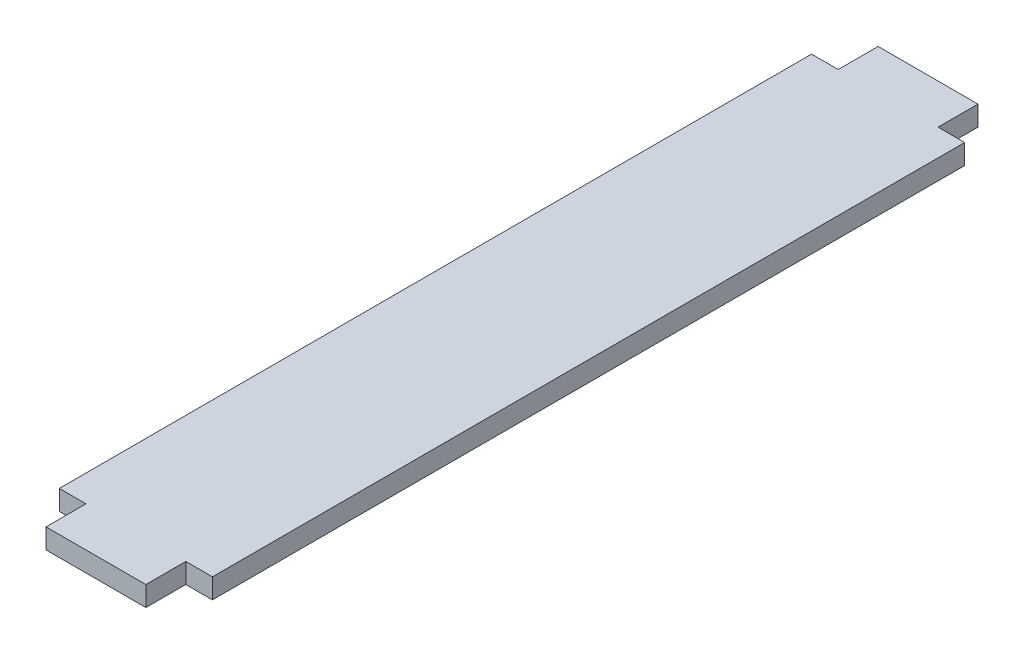
SolidWorks part; units mm, degrees
material "AISI 304"
ref_plane "Front Plane" through (0, 0, 0) normal (0, 0, 1) x (1, 0, 0)
ref_plane "Top Plane" through (0, 0, 0) normal (0, 1, 0) x (1, 0, 0)
ref_plane "Right Plane" through (0, 0, 0) normal (1, 0, 0) x (0, 0, -1)
sketch "Sketch1" plane through (0, 0, 0) normal (0, 1, 0) x (1, 0, 0)
  line L0 (3.75, 28.25) -> (5.75, 28.25)
  line L1 (-5.75, -28.25) -> (-3.75, -28.25)
  line L2 (-5.75, -28.25) -> (-5.75, -18.35)
  line L3 (-5.75, 28.25) -> (-3.75, 28.25)
  line L4 (5.75, -28.25) -> (5.75, -13.35)
  line L5 (-5.75, -28.25) -> (5.75, 28.25) construction
  line L6 (-5.75, 28.25) -> (5.75, -28.25) construction
  line L8 (3.75, 28.25) -> (3.75, 31.25)
  line L9 (3.75, 31.25) -> (-3.75, 31.25)
  line L10 (-3.75, 28.25) -> (-3.75, 31.25)
  line L12 (-3.75, -28.25) -> (-3.75, -31.25)
  line L13 (-3.75, -31.25) -> (3.75, -31.25)
  line L14 (3.75, -28.25) -> (3.75, -31.25)
  line L15 (3.75, -28.25) -> (5.75, -28.25)
  line L16 (-5.75, -16.65) -> (-5.75, 28.25)
  line L21 (5.75, -11.65) -> (5.75, 28.25)
  line L26 (-5.75, -18.35) -> (-5.75, -16.65)
  line L27 (5.75, -13.35) -> (5.75, -11.65)
  point P0 (0, 0)
  dimension "D1" = 7.5
  dimension "D2" = 2
  dimension "D3" = 2
  dimension "D4" = 3
  dimension "D5" = 2
  dimension "D6" = 2
  dimension "D7" = 3
  dimension "D8" = 56.5
extrude "Boss-Extrude1" add sketch "Sketch1" along normal blind 1.5
